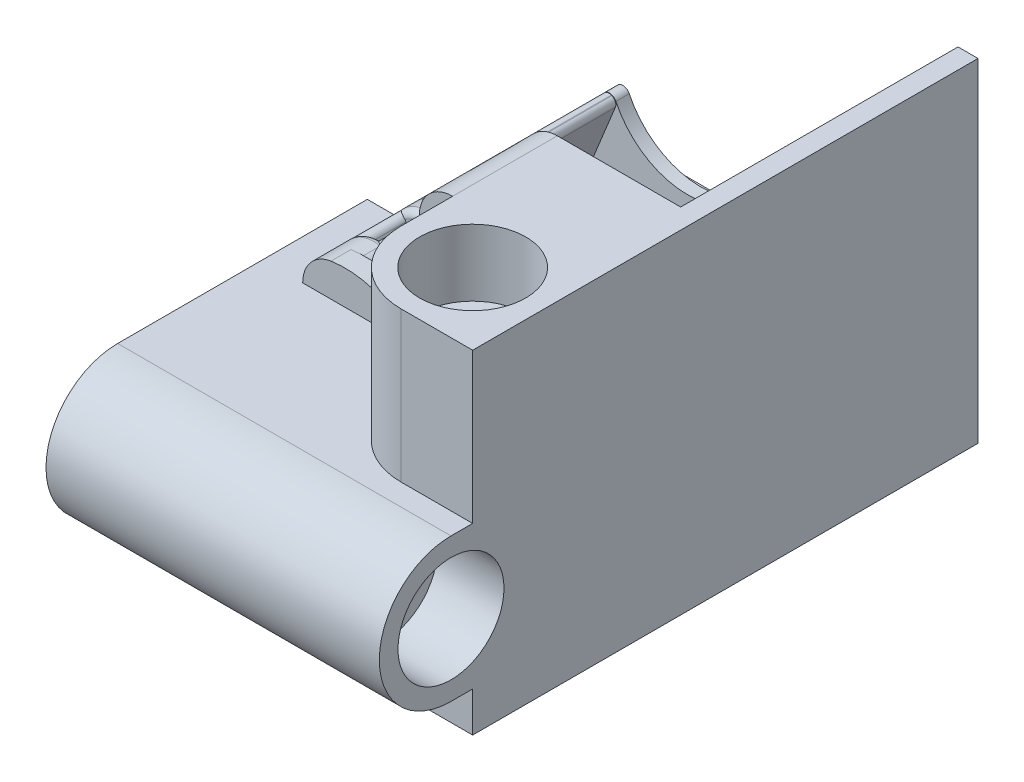
SolidWorks part; units mm, degrees
material "ABS"
ref_plane "Front Plane" through (0, 0, 0) normal (0, 0, 1) x (1, 0, 0)
ref_plane "Top Plane" through (0, 0, 0) normal (0, 1, 0) x (1, 0, 0)
ref_plane "Right Plane" through (0, 0, 0) normal (1, 0, 0) x (0, 0, -1)
sketch "Sketch1" plane through (0, 0, 0) normal (0, 0, 1) x (1, 0, 0)
  line L1 (-25, -25) -> (25, -25)
  line L2 (-25, -25) -> (-25, 25)
  line L3 (-25, 25) -> (25, 25)
  line L4 (25, -25) -> (25, 25)
  line L5 (-25, -25) -> (25, 25) construction
  line L6 (-25, 25) -> (25, -25) construction
  point P0 (0, 0)
  dimension "D1" = 50
  dimension "D2" = 50
extrude "Boss-Extrude1" add sketch "Sketch1" along normal blind 5
sketch "Sketch2" plane through (0, 0, 0) normal (0, 1, 0) x (1, 0, 0)
  line L0 (14.25, -15.75) -> (25, -15.75) construction
  line L1 (3.5, -5) -> (25, -5)
  line L2 (25, -5) -> (-25, -5) construction
  line L3 (25, -5) -> (25, 0) construction
  line L4 (25, -15.75) -> (25, -5)
  line L5 (3.5, -15.75) -> (3.5, -5)
  line L6 (25, -15.75) -> (25, -26.5)
  line L7 (25, -26.5) -> (14.25, -26.5)
  arc A1 (3.5, -15.75) -> (14.25, -26.5) centre (14.25, -15.75) ccw
  dimension "D2" = 21.5
extrude "Boss-Extrude2" add sketch "Sketch2" along normal up to surface and the other way up to surface up to face at (0, 25, 2.5) other way up to face at (0, -25, 2.5)
ref_axis "Axis1" through (14.25, 25, 15.75) along (0, -1, 0)
sketch "Sketch3" plane through (0, 0, 0) normal (1, 0, 0) x (0, 0, -1)
  line L0 (-29.75, 2.5) -> (-5, 2.5)
  line L1 (-5, 25) -> (-5, -25) construction
  line L2 (-29.75, -19) -> (-5, -19)
  line L3 (-5, 25) -> (-5, -25) construction
  line L4 (-5, -19) -> (-5, 2.5)
  line L5 (-15.75, 25) -> (-15.75, -25) construction
  line L6 (-15.75, -25) -> (-5, -25) construction
  arc A0 (-29.75, 2.5) -> (-29.75, -19) centre (-29.75, -8.25) ccw
  dimension "D1" = 21.5
  dimension "D2" = 14
  dimension "D3" = 6
extrude "Boss-Extrude3" add sketch "Sketch3" along normal up to surface and the other way up to surface up to face at (25, 0, 13.25) other way up to face at (-25, 0, 2.5)
ref_axis "Axis2" through (25, -8.25, 29.75) along (-1, 0, 0)
sketch "Sketch4" plane through (0, -25, 0) normal (0, -1, 0) x (1, 0, 0)
  circle A0 centre (14.25, 15.75) radius 5
  dimension "D1" = 10
extrude "Cut-Extrude1" cut sketch "Sketch4" against normal up to surface (50 mm away) up to face at (4.7534, 25, 12.3359)
sketch "Sketch5" plane through (0, -25, 0) normal (0, -1, 0) x (1, 0, 0)
  circle A0 centre (14.25, 15.75) radius 7.95
  dimension "D1" = 15.9
extrude "Cut-Extrude2" cut sketch "Sketch5" against normal blind 10
sketch "Sketch6" plane through (0, 25, 0) normal (0, 1, 0) x (1, 0, 0)
  circle A0 centre (14.25, -15.75) radius 7.95
  dimension "D1" = 15.9
extrude "Cut-Extrude3" cut sketch "Sketch6" against normal blind 10
sketch "Sketch7" plane through (25, 0, 0) normal (1, 0, 0) x (0, 0, -1)
  circle A0 centre (-29.75, -8.25) radius 5
  dimension "D1" = 10
extrude "Cut-Extrude4" cut sketch "Sketch7" against normal up to surface (50 mm away) up to face at (-25, -4.125, 11.2812)
sketch "Sketch8" plane through (25, 0, 0) normal (1, 0, 0) x (0, 0, -1)
  circle A0 centre (-29.75, -8.25) radius 7.95
  dimension "D1" = 15.9
extrude "Cut-Extrude5" cut sketch "Sketch8" against normal blind 10
sketch "Sketch9" plane through (-25, 0, 0) normal (-1, 0, 0) x (0, 0, 1)
  circle A0 centre (29.75, -8.25) radius 7.95
  dimension "D1" = 15.9
extrude "Cut-Extrude6" cut sketch "Sketch9" against normal blind 10
sketch "Sketch10" plane through (0, 0, 5) normal (0, 0, 1) x (1, 0, 0)
  line L0 (3.5, 2.5) -> (-5, 11) construction
  line L1 (3.5, 25) -> (-25, 25)
  line L2 (-25, 2.5) -> (-19, 2.5)
  line L4 (-25, 2.5) -> (3.5, 2.5)
  line L5 (3.5, 2.5) -> (3.5, 25)
  line L6 (3.5, 25) -> (-25, 25)
  line L7 (-25, 25) -> (-25, 2.5)
  line L8 (-25, 2.5) -> (3.5, 2.5)
  line L9 (3.5, 2.5) -> (3.5, 25)
  line L10 (3.5, 25) -> (-25, 25)
  line L11 (-25, 25) -> (-25, 2.5)
  arc A0 (-11.7656, 6.5462) -> (-0.5462, 17.7656) centre (-5, 11) ccw
  arc A1 (3.5, 25) -> (-1.4109, 19.0603) centre (3.5, 20) ccw
  arc A2 (-0.5462, 17.7656) -> (-1.4109, 19.0603) centre (0.5535, 19.4362) cw
  arc A3 (-19, 2.5) -> (-13.0603, 7.4109) centre (-14, 2.5) cw
  arc A4 (-11.7656, 6.5462) -> (-13.0603, 7.4109) centre (-13.4362, 5.4465) ccw
  line M5 (-25, 2.5) -> (3.5, 2.5)
  line M7 (3.5, 25) -> (-25, 25)
  line M8 (-25, 25) -> (-25, 2.5)
  dimension "D2" = 16.2
  dimension "D3" = 5
  dimension "D4" = 2
  dimension "D1" = 0
extrude "Cut-Extrude7" cut sketch "Sketch10" against normal up to surface (5 mm away) contours A4 A0 A2 A1 A3 M7 M8 M5 region at (-11.9115, 14.3488, 5) up to face at (0, 0, 0)
sketch "Sketch11" plane through (0, 0, 5) normal (0, 0, 1) x (1, 0, 0)
  line L0 (3.5, 2.5) -> (-5, 11) construction
  line L1 (3.5, 25) -> (3.5, 2.5) construction
  line L2 (3.5, 2.5) -> (-19, 2.5) construction
  line L3 (3.5, 25) -> (3.5, 2.5)
  line L4 (3.5, 2.5) -> (-19, 2.5)
  arc A0 (-7.0104, 6.422) -> (-0.422, 13.0104) centre (-5, 11) ccw
  arc A1 (-1.4425, 20.7559) -> (-0.422, 13.0104) centre (12.3966, 18.6394) ccw
  arc A2 (-14.7559, 7.4425) -> (-7.0104, 6.422) centre (-12.6394, -6.3966) cw
  arc A4 (3.5, 25) -> (-1.4109, 19.0603) centre (3.5, 20) ccw construction
  arc A10 (-13.0603, 7.4109) -> (-19, 2.5) centre (-14, 2.5) ccw construction
  arc A11 (3.5, 25) -> (-1.4425, 20.7559) centre (3.5, 20) ccw
  arc A12 (-14.7559, 7.4425) -> (-19, 2.5) centre (-14, 2.5) ccw
  dimension "D1" = 10
  dimension "D2" = 14
extrude "Boss-Extrude4" add sketch "Sketch11" along normal blind 3
sketch "Sketch14" plane through (25, 0, 0) normal (1, 0, 0) x (0, 0, -1)
  line L0 (-26.5, -25) -> (0, -25) construction
  line L1 (0, 25) -> (49.3, 25)
  line L2 (0, 25) -> (0, -25)
  line L3 (0, -25) -> (49.3, -25)
  line L4 (49.3, 25) -> (49.3, -25)
  line L5 (49.3, -11.0918) -> (49.3, -12) construction
extrude "Boss-Extrude6" add sketch "Sketch14" against normal blind 3
sketch "Sketch15" plane through (0, 0, 0) normal (0, 0, -1) x (-1, 0, 0)
  line L0 (-13.95, -15.2) -> (-16.5, -15.2) construction
  line L1 (-22, -25) -> (-16.5, -25)
  line L2 (-22, -25) -> (-22, -15.2)
  line L3 (-22, -15.2) -> (-16.5, -15.2)
  line L4 (-16.5, -25) -> (-16.5, -15.2)
  line L5 (-12, -15.2) -> (-15.9, -15.2) construction
  line L6 (-16, -14.938) -> (-16, -27.1841) construction
  dimension "D1" = 0.5
extrude "Boss-Extrude7" add sketch "Sketch15" along normal up to surface (49.3 mm away) up to face at (23.5, 0, -49.3)
sketch "Sketch16" plane through (0, -15.2, 0) normal (0, 1, 0) x (1, 0, 0)
  line L1 (22, 0) -> (-25, 0)
  line L2 (22, 0) -> (22, 49.3)
  line L3 (22, 49.3) -> (-25, 49.3)
  line L4 (-25, 0) -> (-25, 49.3)
  line L5 (16.5, 49.3) -> (22, 49.3) construction
  line L7 (-25, -5) -> (-25, 0) construction
extrude "Boss-Extrude8" add sketch "Sketch16" along normal blind 3
sketch "Sketch17" plane through (0, 0, 0) normal (0, 0, -1) x (-1, 0, 0)
  line L5 (-22, -12.2) -> (25, -12.2)
  line L6 (25, -12.2) -> (25, 2.5)
  line L7 (25, 2.5) -> (19, 2.5)
  line L8 (-3.5, 25) -> (-22, 25)
  line L9 (-22, 25) -> (-22, -12.2)
  line L10 (-22, -12.2) -> (25, -12.2)
  line L11 (25, -12.2) -> (25, 2.5)
  line L12 (25, 2.5) -> (19, 2.5)
  line L13 (-3.5, 25) -> (-22, 25)
  line L14 (-22, 25) -> (-22, -12.2)
  arc A5 (19, 2.5) -> (13.0603, 7.4109) centre (14, 2.5) ccw
  arc A6 (13.0603, 7.4109) -> (11.7656, 6.5462) centre (13.4362, 5.4465) ccw
  arc A7 (0.5462, 17.7656) -> (11.7656, 6.5462) centre (5, 11) ccw
  arc A8 (0.5462, 17.7656) -> (1.4109, 19.0603) centre (-0.5535, 19.4362) ccw
  arc A9 (1.4109, 19.0603) -> (-3.5, 25) centre (-3.5, 20) ccw
  arc A10 (19, 2.5) -> (13.0603, 7.4109) centre (14, 2.5) ccw
  arc A11 (13.0603, 7.4109) -> (11.7656, 6.5462) centre (13.4362, 5.4465) ccw
  arc A12 (0.5462, 17.7656) -> (11.7656, 6.5462) centre (5, 11) ccw
  arc A13 (0.5462, 17.7656) -> (1.4109, 19.0603) centre (-0.5535, 19.4362) ccw
  arc A14 (1.4109, 19.0603) -> (-3.5, 25) centre (-3.5, 20) ccw
  dimension "D1" = 0
extrude "Boss-Extrude9" add sketch "Sketch17" along normal blind 7.7
ref_plane "Plane1" through (0, 0, 1.3) normal (0, 0, -1) x (-1, 0, 0)
ref_plane "Plane2" through (0, 0, -4.7) normal (0, 0, 1) x (1, 0, 0)
sketch "Sketch18" plane through (0, 0, 1.3) normal (0, 0, -1) x (-1, 0, 0)
  line L0 (0.722, 15.278) -> (-0.7276, 16.7276)
  line L1 (-1.05, 11) -> (23.1459, 11) construction
  line L2 (9.278, 6.722) -> (10.7276, 5.2724)
  arc A0 (0.722, 15.278) -> (9.278, 6.722) centre (5, 11) ccw
  arc A1 (0.5462, 17.7656) -> (11.7656, 6.5462) centre (5, 11) ccw construction
  arc A2 (-0.7276, 16.7276) -> (10.7276, 5.2724) centre (5, 11) ccw
  dimension "D1" = 12.1
  dimension "D2" = 45
  dimension "D3" = 180
extrude "Boss-Extrude10" add sketch "Sketch18" along normal up to surface (6 mm away) up to plane "Plane2"
ref_plane "Plane3" through (-5, 0, 0) normal (-1, 0, 0) x (0, 0, 1)
sketch "Sketch19" plane through (-5, 0, 0) normal (-1, 0, 0) x (0, 0, 1)
  line L0 (1.3, 8.8) -> (1.3, -8.8) construction
  line L1 (1.3, 21.5) -> (-4.7, 21.5)
  line L2 (1.3, 21.5) -> (1.3, 23.5)
  line L3 (1.3, 23.5) -> (-4.7, 23.5)
  line L4 (-4.7, 21.5) -> (-4.7, 23.5)
  line L5 (-4.7, -8.8) -> (-4.7, 8.8) construction
  line L6 (16.2565, 11) -> (-48.8952, 11) construction
  dimension "D1" = 10.5
  dimension "D2" = 2
ref_axis "Axis3" through (-5, 11, 8) along (0, 0, -1)
revolve "Cut-Revolve1" cut sketch "Sketch19" angle 360 about axis through (-5, 11, 8) along (0, 0, -1)
fillet "Fillet1" radius 1 8 edges at (-16.7325, 6.6873, -1.7) (-15.8395, 7.1493, -4.7) (-14.8721, 7.4234, -1.7) (-15.8395, 7.1493, 1.3) (-1.1493, 21.8395, 1.3) (-0.6873, 22.7325, -1.7) (-1.1493, 21.8395, -4.7) (-1.4234, 20.8721, -1.7)
sketch "Sketch20" plane through (0, 0, -7.7) normal (0, 0, -1) x (-1, 0, 0)
  line L0 (-16.5, -12.2) -> (-6.6946, 7.8976)
  line L1 (-22, -12.2) -> (25, -12.2) construction
  line L2 (-7.1318, 9.1679) -> (-7.2217, 9.2118)
  line L3 (-8.4921, 8.7746) -> (-18.7253, -12.2)
  line L4 (-18.7253, -12.2) -> (-16.5, -12.2)
  line L5 (-16.5, -25) -> (-16.5, -15.2) construction
  line L6 (25, -12.2) -> (17.6463, 5.8167)
  line L7 (16.4077, 6.3372) -> (16.3151, 6.2995)
  line L8 (15.7946, 5.0609) -> (22.8398, -12.2)
  line L9 (22.8398, -12.2) -> (25, -12.2)
  circle A1 centre (5, 11) radius 11.15 construction
  circle A2 centre (5, 11) radius 11.15 construction
  arc A3 (-8.4921, 8.7746) -> (-7.2217, 9.2118) centre (-7.6383, 8.358) cw
  arc A4 (-7.1318, 9.1679) -> (-6.6946, 7.8976) centre (-7.5484, 8.3141) cw
  arc A5 (15.7946, 5.0609) -> (16.3151, 6.2995) centre (16.6741, 5.4199) cw
  arc A6 (16.4077, 6.3372) -> (17.6463, 5.8167) centre (16.7667, 5.4577) cw
  arc A7 (19, 2.5) -> (13.0603, 7.4109) centre (14, 2.5) ccw construction
  arc A8 (19, 2.5) -> (13.0603, 7.4109) centre (14, 2.5) ccw construction
  point P17 (-6.278, 8.7514)
  dimension "D2" = 11.5
  dimension "D3" = 0.95
  dimension "D5" = 0.95
  dimension "D1" = 2
  dimension "D4" = 2
extrude "Boss-Extrude11" add sketch "Sketch20" along normal blind 30
sketch "Sketch21" plane through (0, 0, -37.7) normal (0, 0, -1) x (-1, 0, 0)
  line L0 (-18.7253, -12.2) -> (-8.4921, 8.7746)
  line L1 (25, -12.2) -> (17.6463, 5.8167)
  line L2 (-18.7253, -12.2) -> (25, -12.2)
  arc A0 (-6.6136, 8.4857) -> (15.7156, 5.8647) centre (5, 11) ccw
  arc A1 (-6.6946, 7.8976) -> (-7.1318, 9.1679) centre (-7.5484, 8.3141) ccw construction
  arc A2 (17.6463, 5.8167) -> (15.7156, 5.8647) centre (16.6702, 5.4073) ccw
  arc A3 (-8.4921, 8.7746) -> (-6.6136, 8.4857) centre (-7.6081, 8.2704) cw
  dimension "D1" = 1.0585
extrude "Boss-Extrude12" add sketch "Sketch21" against normal blind 2
